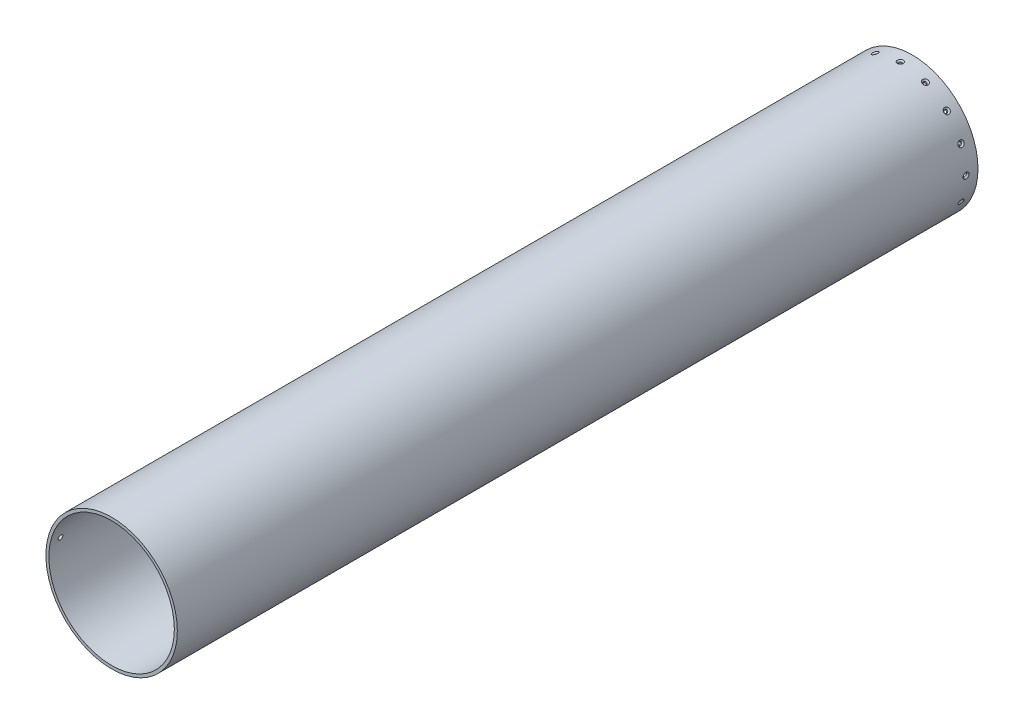
SolidWorks part; units mm, degrees
material "6061-T6 (SS)"
ref_plane "Front Plane" through (0, 0, 0) normal (0, 0, 1) x (1, 0, 0)
ref_plane "Top Plane" through (0, 0, 0) normal (0, 1, 0) x (1, 0, 0)
ref_plane "Right Plane" through (0, 0, 0) normal (1, 0, 0) x (0, 0, -1)
sketch "Sketch1" plane through (0, 0, 0) normal (0, 0, 1) x (1, 0, 0)
  circle A0 centre (0, 0) radius 69.85
  circle A1 centre (0, 0) radius 66.675
extrude "Extrude1" add sketch "Sketch1" along normal blind 850.9
ref_plane "Plane1" through (0, 0, 12.7) normal (0, 0, -1) x (-1, 0, 0)
sketch "Sketch2" plane through (0, 0, 12.7) normal (0, 0, -1) x (-1, 0, 0)
  line L0 (0, 0) -> (0, -69.85) construction
  circle A0 centre (0, 0) radius 69.85 construction
ref_plane "Plane2" through (0, -69.85, 12.7) normal (0, -1, 0) x (1, 0, 0)
hole_wizard "CSK for M3 Flat Head Machine Screw1" positions "Sketch5" profile "Sketch4" countersink size "M3" standard "Ansi Metric" end condition through all
sketch "Sketch5" plane through (0, -69.85, 12.7) normal (0, -1, 0) x (1, 0, 0)
  point P2 (0, 0)
sketch "Sketch4" plane through (0, -69.85, 12.7) normal (1, 0, 0) x (0, 0, -1)
  line L0 (0, 0) -> (0, 161.1134)
  line L1 (0, 161.1134) -> (1.7, 161.1134)
  line L2 (1.7, 161.1134) -> (1.7, 1.45)
  line L3 (1.7, 1.45) -> (3.15, 0)
  line L5 (3.15, 0) -> (0, 0)
  line L6 (-1.7, 1.45) -> (-3.15, 0) construction
  line L11 (0, -6.35) -> (0, 107.95) construction
  dimension "Thru Hole Dia." = 3.4
  dimension "Thru Hole Depth" = 161.1134
  dimension "Near C'Sink Dia." = 6.3
  dimension "Near C'Sink Angle" = 90
pattern_circular "CirPattern1" count 16 over 360 about axis through (0, 0, 850.9) along (0, 0, -1) of "CSK for M3 Flat Head Machine Screw1"
ref_plane "Plane3" through (0, 0, 839.7875) normal (0, 0, 1) x (1, 0, 0)
ref_plane "Plane5" through (0, 0, 0) normal (0.8315, 0.5556, 0) x (-0.5556, 0.8315, 0)
ref_plane "Plane7" through (0, 0, 0) normal (0.5556, -0.8315, 0) x (0.8315, 0.5556, 0)
ref_plane "Plane9" through (0, 0, 0) normal (-0.1951, -0.9808, 0) x (0.9808, -0.1951, 0)
sketch "Sketch7" plane through (0, 0, 850.9) normal (0, 0, 1) x (1, 0, 0)
  circle A0 centre (0, 0) radius 69.85 construction
  point P0 (69.85, 0)
ref_plane "Plane8" through (-68.5079, 13.6271, 425.45) normal (-0.9808, 0.1951, 0) x (0.1951, 0.9808, 0)
sketch "Sketch8" plane through (-68.5079, 13.6271, 425.45) normal (-0.9808, 0.1951, 0) x (0.1951, 0.9808, 0)
  line L0 (0, -425.45) -> (0, -414.3248) construction
hole_wizard "#7 (0.201) Diameter Hole1" positions "Sketch10" profile "Sketch9" hole size "#7" standard "Ansi Inch"
sketch "Sketch10" plane through (-68.5079, 13.6271, 425.45) normal (-0.9808, 0.1951, 0) x (0.1951, 0.9808, 0)
  point P1 (0, -414.3248)
sketch "Sketch9" plane through (-68.5079, 13.6271, 839.7748) normal (0, 0, 1) x (-0.1951, -0.9808, 0)
  line L0 (0, 0) -> (0, 11.6938)
  line L1 (0, 11.6938) -> (2.5527, 10.16)
  line L2 (2.5527, 10.16) -> (2.5527, 0)
  line L5 (2.5527, 0) -> (0, 0)
  line L10 (0, 11.6938) -> (-2.5527, 10.16) construction
  line L11 (0, -6.35) -> (0, 107.95) construction
  dimension "Hole Dia." = 5.1054
  dimension "Hole Depth" = 10.16
  dimension "Drill Angle" = 118
